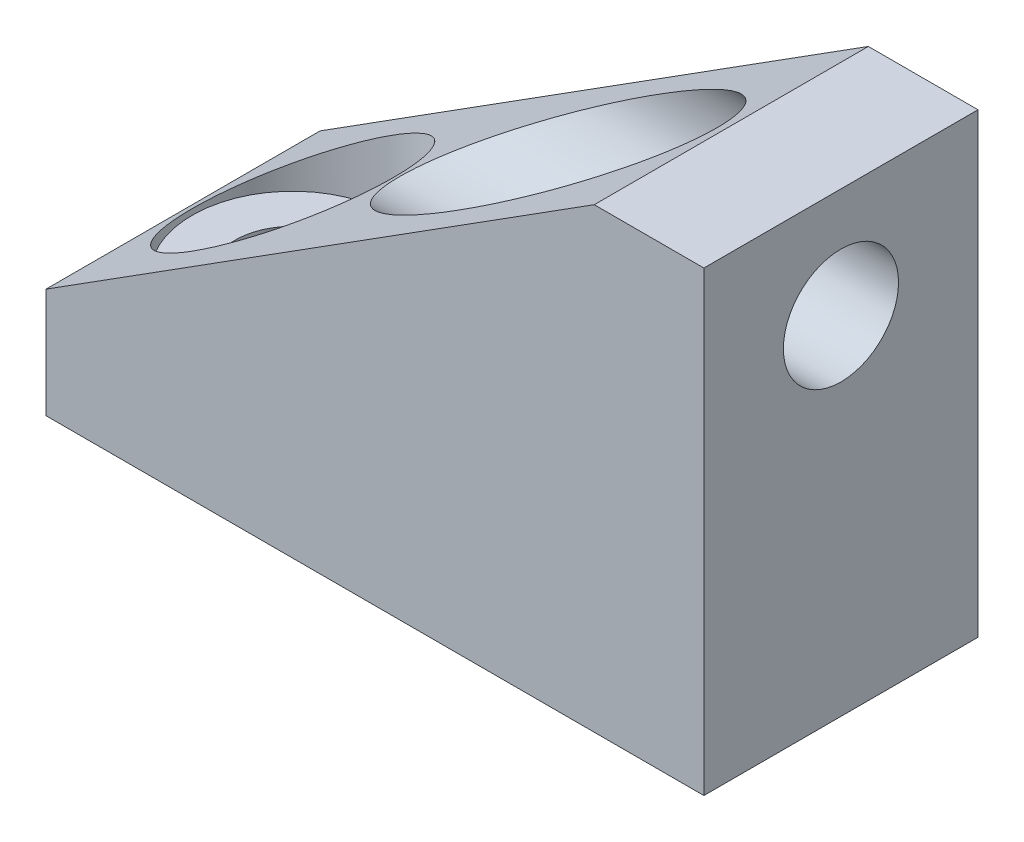
SolidWorks part; units mm, degrees
ref_plane "Front Plane" through (0, 0, 0) normal (0, 0, 1) x (1, 0, 0)
ref_plane "Top Plane" through (0, 0, 0) normal (0, 1, 0) x (1, 0, 0)
ref_plane "Right Plane" through (0, 0, 0) normal (1, 0, 0) x (0, 0, -1)
sketch "Sketch3" plane through (0, 0, 0) normal (0, 0, 1) x (1, 0, 0)
  line L0 (2.3468, 0) -> (38.3468, 0)
  line L1 (55, 0) -> (-55, 0) construction
  line L2 (38.3468, 0) -> (38.3468, 25)
  line L4 (2.3468, 0) -> (2.3468, 6)
  line L6 (38.3468, 25) -> (32.3468, 25)
  line L8 (2.3468, 6) -> (32.3468, 25)
  dimension "D1" = 36
  dimension "D2" = 25
  dimension "D3" = 6
  dimension "D4" = 6
extrude "Boss-Extrude2" add sketch "Sketch3" along normal blind 15 contours L4 | L2 L0 region at (24.0542, 9.6423, 0)
ref_plane "Plane1" through (0, 20, 0) normal (0, 1, 0) x (1, 0, 0)
sketch "Sketch4" plane through (0, 20, 0) normal (0, 1, 0) x (1, 0, 0)
  line L1 (38.3468, -15) -> (38.3468, 0) construction
  line L2 (-55, 0) -> (55, 0) construction
  circle A0 centre (8.3468, -7.5) radius 3.15
  circle A1 centre (8.3468, -7.5) radius 5.5
  dimension "D1" = 6.3
  dimension "D2" = 11
  dimension "D3" = 30
  dimension "D4" = 7.5
extrude "Cut-Extrude1" cut sketch "Sketch4" against normal through all contours A0 region at (8.3468, 20, 7.5)
extrude "Cut-Extrude2" cut sketch "Sketch4<3>" against normal blind 14
sketch "Sketch4<3>" plane through (0, 20, 0) normal (0, 1, 0) x (1, 0, 0) same geometry as "Sketch4"
sketch "Sketch6" plane through (0, 0, 0) normal (1, 0, 0) x (0, 0, -1)
  line L1 (8.25, 0) -> (-8.25, 0) construction
  line L2 (-15, 0) -> (-15, 25) construction
  circle A0 centre (-7.5, 19) radius 3.15
  circle A1 centre (-7.5, 19) radius 5.5
  dimension "D1" = 6.3
  dimension "D2" = 11
  dimension "D3" = 19
  dimension "D4" = 7.5
extrude "Cut-Extrude3" cut sketch "Sketch6" along normal through all contours A0 region at (0, 19, 7.5)
extrude "Cut-Extrude4" cut sketch "Sketch6<3>" along normal offset from surface (32.3468 mm away) 6 up to face at (38.3468, 19, 4.35)
sketch "Sketch6<3>" plane through (0, 0, 0) normal (1, 0, 0) x (0, 0, -1) same geometry as "Sketch6"
